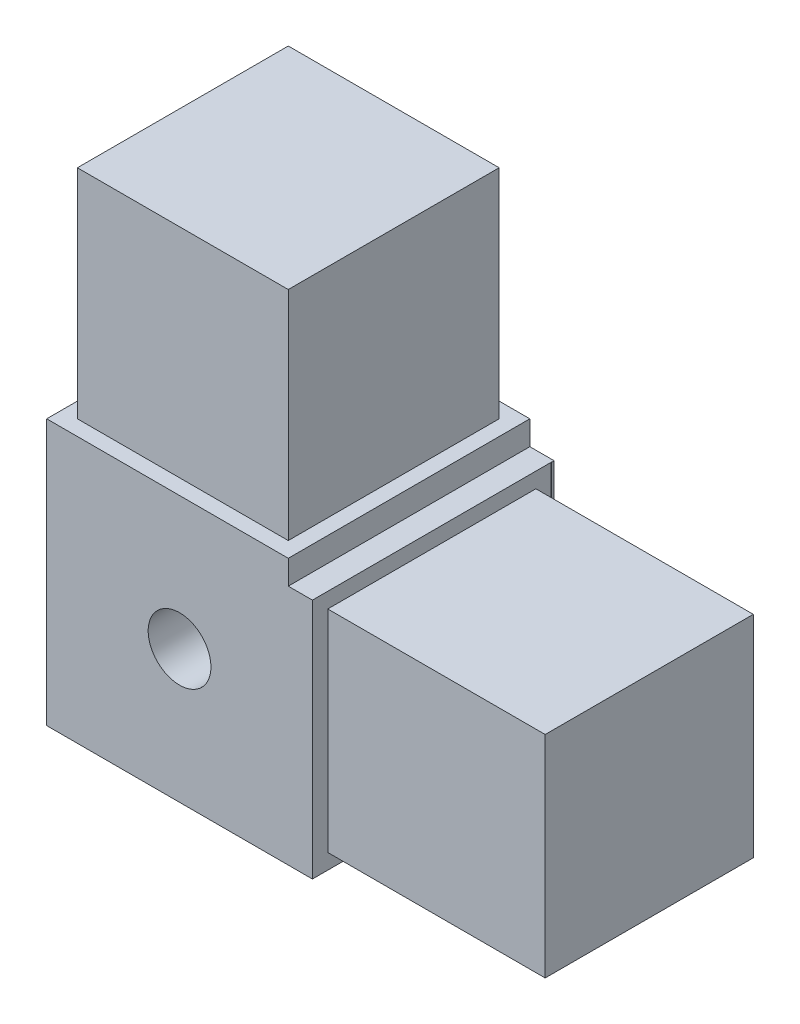
SolidWorks part; units mm, degrees
material "ALUMINUM 6061-T6"
ref_plane "Front Plane" through (0, 0, 0) normal (0, 0, 1) x (1, 0, 0)
ref_plane "Top Plane" through (0, 0, 0) normal (0, 1, 0) x (1, 0, 0)
ref_plane "Right Plane" through (0, 0, 0) normal (1, 0, 0) x (0, 0, -1)
sketch "Sketch1" plane through (0, 0, 0) normal (0, 0, 1) x (1, 0, 0)
  line L1 (-25.4, -25.4) -> (25.4, -25.4)
  line L2 (-25.4, -25.4) -> (-25.4, 25.4)
  line L3 (-25.4, 25.4) -> (25.4, 25.4)
  line L4 (25.4, -25.4) -> (25.4, 25.4)
  line L5 (-25.4, -25.4) -> (25.4, 25.4) construction
  line L6 (-25.4, 25.4) -> (25.4, -25.4) construction
  point P0 (0, 0)
  dimension "D1" = 50.8
  dimension "D2" = 50.8
extrude "Boss-Extrude1" add sketch "Sketch1" along normal mid plane 25.4
sketch "Sketch2" plane through (0, 0, 12.7) normal (0, 0, 1) x (1, 0, 0)
  line L1 (25.4, 25.4) -> (0, 25.4)
  line L2 (25.4, 25.4) -> (25.4, 0)
  line L3 (25.4, 0) -> (0, 0)
  line L4 (0, 25.4) -> (0, 0)
extrude "Cut-Extrude1" cut sketch "Sketch2" against normal through all
sketch "Sketch3" plane through (25.4, 0, 0) normal (1, 0, 0) x (0, 0, -1)
  line L0 (12.7, 0) -> (-12.7, 0) construction
  line L1 (-12.7, -25.4) -> (12.4098, -25.4)
  line L2 (-12.7, -25.4) -> (-12.7, 0)
  line L3 (-12.7, 0) -> (12.4098, 0)
  line L4 (12.4098, -25.4) -> (12.4098, 0)
  line L5 (-11.0871, -23.7871) -> (-11.0871, -1.6129)
  line L6 (-11.0871, -1.6129) -> (10.7969, -1.6129)
  line L7 (10.7969, -23.7871) -> (10.7969, -1.6129)
  line L8 (-11.0871, -23.7871) -> (10.7969, -23.7871)
  dimension "D1" = 1.6129
extrude "Cut-Extrude2" cut sketch "Sketch3" against normal blind 22.86
sketch "Sketch5" plane through (0, 25.4, 0) normal (0, 1, 0) x (1, 0, 0)
  line L0 (-1.6129, 11.0871) -> (-23.7871, 11.0871)
  line L1 (0, -12.7) -> (-25.4, -12.7)
  line L2 (0, -12.7) -> (0, 12.7)
  line L3 (0, 12.7) -> (-25.4, 12.7)
  line L4 (-25.4, -12.7) -> (-25.4, 12.7)
  line L5 (-23.7871, -11.0871) -> (-23.7871, 11.0871)
  line L6 (-1.6129, -11.0871) -> (-23.7871, -11.0871)
  line L7 (-1.6129, -11.0871) -> (-1.6129, 11.0871)
  dimension "D1" = 1.6129
extrude "Cut-Extrude4" cut sketch "Sketch5" against normal blind 22.86
sketch "Sketch6" plane through (0, 0, -12.7) normal (0, 0, -1) x (-1, 0, 0)
  line L0 (0, 0) -> (-25.4, 0) construction
  line L1 (-25.4, -25.4) -> (-2.5647, -25.4)
  line L2 (-25.4, -25.4) -> (-25.4, 0)
  line L3 (-25.4, 0) -> (-2.5647, 0)
  line L4 (-2.5647, -25.4) -> (-2.5647, 0)
extrude "Cut-Extrude5" cut sketch "Sketch6" against normal up to body
sketch "Sketch7" plane through (0, 0, 12.7) normal (0, 0, 1) x (1, 0, 0)
  line L0 (-25.4, 2.54) -> (-25.4, -25.4) construction
  line L1 (-25.4, -25.4) -> (2.54, -25.4) construction
  circle A0 centre (-11.43, -11.43) radius 3.3
  dimension "D1" = 6.6
  dimension "D2" = 13.97
  dimension "D3" = 13.97
extrude "Cut-Extrude6" cut sketch "Sketch7" against normal through all
